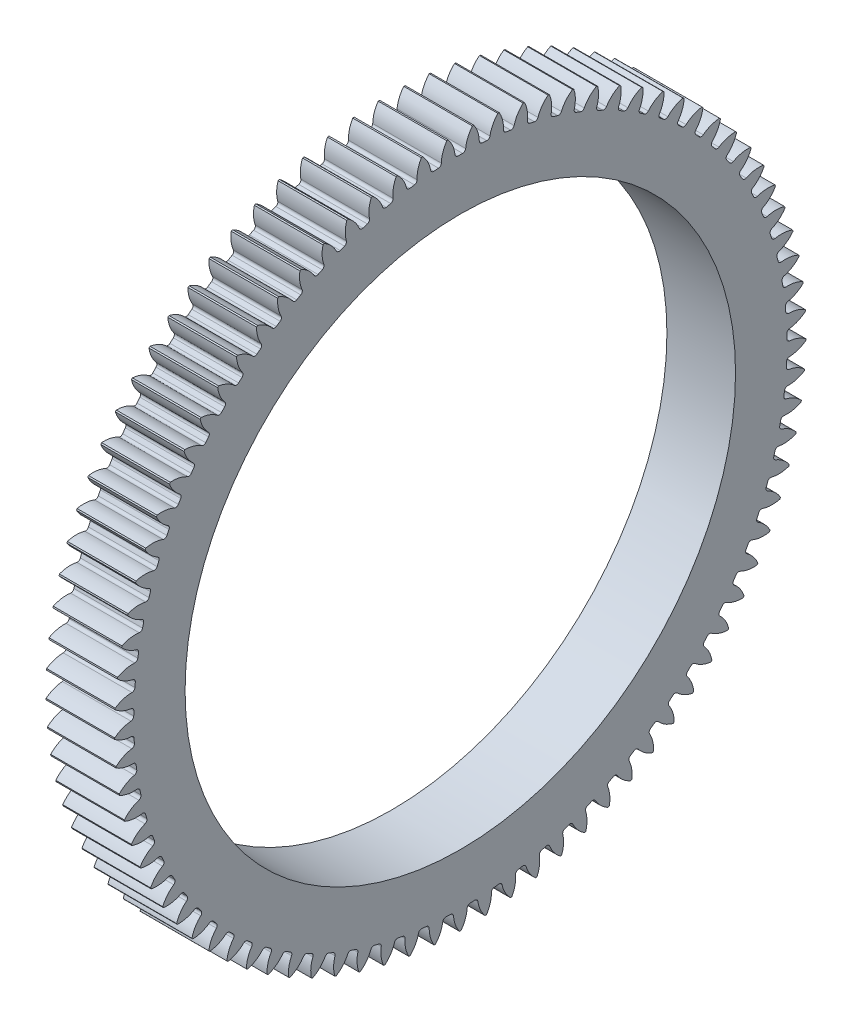
SolidWorks part; units mm, degrees
ref_plane "Front Plane" through (0, 0, 0) normal (0, 0, 1) x (1, 0, 0)
ref_plane "Top Plane" through (0, 0, 0) normal (0, 1, 0) x (1, 0, 0)
ref_plane "Right Plane" through (0, 0, 0) normal (1, 0, 0) x (0, 0, -1)
sketch "Sketch1" plane through (0, 0, 0) normal (1, 0, 0) x (0, 0, -1)
  circle A0 centre (0, 0) radius 38.1
  circle A1 centre (0, 0) radius 47.85
  dimension "D1" = 76.2
  dimension "10mm" = 95.7
extrude "Boss-Extrude2" add sketch "Sketch1" along normal blind 9.5
sketch "Sketch3" plane through (9.5, 0, 0) normal (1, 0, 0) x (0, 0, -1)
  line L0 (0, 0) -> (0, 47.85) construction
  line L1 (-0.7166, 45.2043) -> (0, 0) construction
  line L2 (0, 43.9201) -> (-2.9699, 52.0797) construction
  circle A0 centre (0, 0) radius 47.85 construction
  arc A1 (0.7166, 45.2043) -> (-0.7166, 45.2043) centre (0, 0) ccw
  arc A2 (1.0289, 46.7387) -> (-1.0289, 46.7387) centre (0, 0) ccw construction
  arc A3 (1.6689, 47.8209) -> (-1.6689, 47.8209) centre (0, 0) ccw
  arc A4 (-1.6689, 47.8209) -> (-0.7166, 45.2043) centre (-4.9726, 45.1369) cw
  arc A5 (1.6689, 47.8209) -> (0.7166, 45.2043) centre (4.9726, 45.1369) ccw
  point P17 (-0.9727, 46.5927)
  dimension "D1" = 95.7
  dimension "D2" = 93.5
  dimension "D3" = 2.64
  dimension "D4" = 20
  dimension "D5" = 2.0579
extrude "Cut-Extrude1" cut sketch "Sketch3" against normal through all
fillet "Fillet1" radius 0.418 2 edges at (4.75, 45.2043, -0.7166) (4.75, 45.2043, 0.7166)
pattern_circular "CirPattern2" count 85 over 360 about axis through (9.5, 0, 0) along (1, 0, 0) of "Fillet1", "Cut-Extrude1"
equation "\"No of teeth\"= 85"
equation "\"Module\"= 1.1"
equation "\"Outer Diameter\"= ( \"No of teeth\" + 2 ) * \"Module\""
equation "\"Pitch Diameter\"= \"No of teeth\" * \"Module\""
equation "\"Backlash\"= 0.3 * \"Module\""
equation "\"Arc Length\"= ( ( \"Module\" * pi ) / 2 ) + \"Backlash\""
equation "\"Fillet Radius\"= 0.38 * \"Module\""
equation "\"Bore Diameter\"= 3in"
equation "\"Presseure angle\"= 20"
equation "\"Tooth Depth\"= IIF ( \"Module\" <= 1.25 , 2.4 * \"Module\" , 2.25 * \"Module\" )"
equation "\"D1@Sketch1\"=\"Bore Diameter\""
equation "\"10mm@Sketch1\" = \"Outer Diameter\""
equation "\"D1@Sketch3\"=\"Outer Diameter\""
equation "\"D2@Sketch3\"=\"Pitch Diameter\""
equation "\"D3@Sketch3\"=\"Tooth Depth\""
equation "\"D4@Sketch3\"=\"Presseure angle\""
equation "\"D5@Sketch3\"=\"Arc Length\""
equation "\"D1@Fillet1\"=\"Fillet Radius\""
equation "\"D1@CirPattern2\"=\"No of teeth\""
